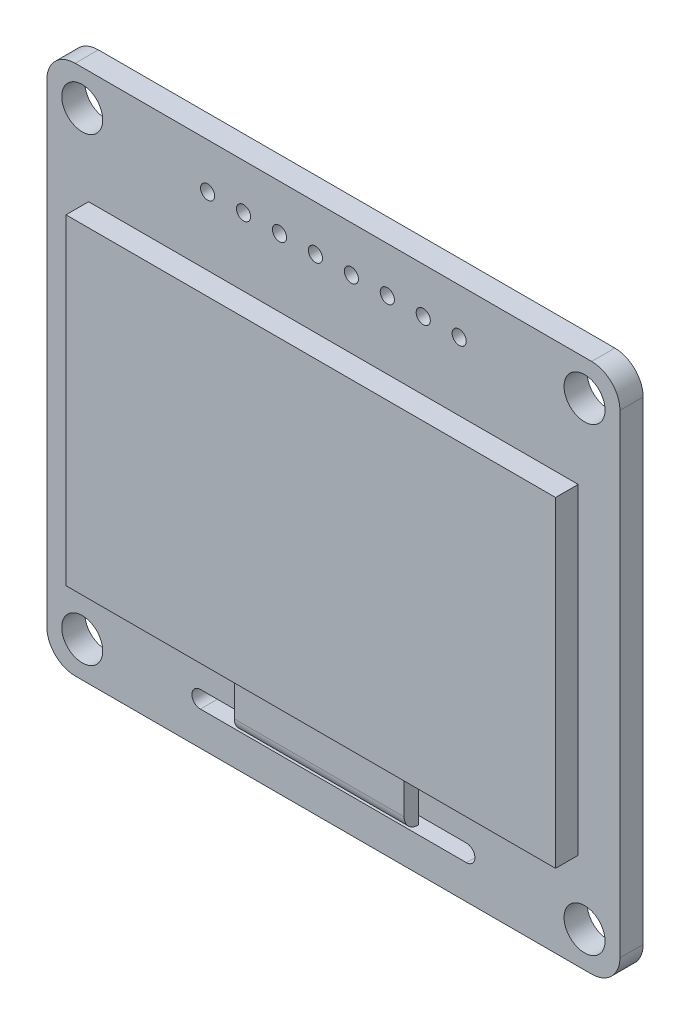
SolidWorks part; units mm, degrees
ref_plane "Front Plane" through (0, 0, 0) normal (0, 0, 1) x (1, 0, 0)
ref_plane "Top Plane" through (0, 0, 0) normal (0, 1, 0) x (1, 0, 0)
ref_plane "Right Plane" through (0, 0, 0) normal (1, 0, 0) x (0, 0, -1)
sketch "Sketch1" plane through (0, 0, 0) normal (0, 0, 1) x (1, 0, 0)
  line L0 (0, 18.75) -> (0, -18.75) construction
  line L1 (-20.25, 18.75) -> (20.25, 18.75)
  line L2 (-20.25, 18.75) -> (-20.25, -18.75)
  line L3 (-20.25, -18.75) -> (20.25, -18.75)
  line L4 (20.25, 18.75) -> (20.25, -18.75)
  point P6 (0, 0)
  dimension "D1" = 40.5
  dimension "D2" = 37.5
extrude "PCB" add sketch "Sketch1" along normal blind 1.64
fillet "Fillet1" radius 2 4 edges at (-20.25, -18.75, 0.82) (20.25, -18.75, 0.82) (20.25, 18.75, 0.82) (-20.25, 18.75, 0.82)
sketch "Sketch2" plane through (0, 0, 1.64) normal (0, 0, 1) x (1, 0, 0)
  line L0 (18.25, 18.75) -> (-18.25, 18.75) construction
  line L1 (-20.25, 16.75) -> (-20.25, -16.75) construction
  line L2 (20.25, -16.75) -> (20.25, 16.75) construction
  line L3 (-18.25, -18.75) -> (18.25, -18.75) construction
  circle A0 centre (-17.75, 16.25) radius 1.45
  circle A1 centre (17.75, 16.25) radius 1.45
  circle A2 centre (17.75, -16.25) radius 1.45
  circle A3 centre (-17.75, -16.25) radius 1.45
  dimension "D1" = 2.5
  dimension "D2" = 2.5
  dimension "D3" = 2.9
  dimension "D6" = 2.5
  dimension "D7" = 2.5
  dimension "D4" = 2
  dimension "D5" = 2
extrude "mount hole" cut sketch "Sketch2" against normal up to next
sketch "Sketch3" plane through (0, 0, 1.64) normal (0, 0, 1) x (1, 0, 0)
  line L0 (-9.4, -15.75) -> (9.4, -15.75) construction
  line L1 (-9.4, -15.15) -> (9.4, -15.15)
  line L2 (-9.4, -16.35) -> (9.4, -16.35)
  line L3 (0, 0) -> (0, -15.75) construction
  line L4 (-18.25, -18.75) -> (18.25, -18.75) construction
  arc A0 (-9.4, -15.15) -> (-9.4, -16.35) centre (-9.4, -15.75) ccw
  arc A1 (9.4, -16.35) -> (9.4, -15.15) centre (9.4, -15.75) ccw
  point P2 (0, -15.75)
  point P10 (10, -15.75)
  point P12 (-10, -15.75)
  dimension "D1" = 20
  dimension "D2" = 1.2
  dimension "D3" = 3
extrude "slot" cut sketch "Sketch3" against normal up to next
sketch "Sketch4" plane through (0, 0, 1.64) normal (0, 0, 1) x (1, 0, 0)
  line L0 (0, 0) -> (0, 18.75) construction
  line L1 (18.25, 18.75) -> (-18.25, 18.75) construction
  line L2 (-8.89, 15.55) -> (-6.35, 15.55) construction
  circle A0 centre (-8.89, 15.55) radius 0.5
  circle A1 centre (-6.35, 15.55) radius 0.5
  circle A2 centre (-3.81, 15.55) radius 0.5
  circle A3 centre (-1.27, 15.55) radius 0.5
  circle A4 centre (1.27, 15.55) radius 0.5
  circle A5 centre (3.81, 15.55) radius 0.5
  circle A6 centre (6.35, 15.55) radius 0.5
  circle A7 centre (8.89, 15.55) radius 0.5
  dimension "D2" = 1
  dimension "D5" = 1.27
  dimension "D1" = 3.2
  dimension "D4" = 2.54
  dimension "D3" = 8
extrude "Cut-Extrude3" cut sketch "Sketch4" against normal up to next
sketch "Sketch5" plane through (0, 0, 1.64) normal (0, 0, 1) x (1, 0, 0)
  line L0 (0, 10.75) -> (0, 18.75) construction
  line L1 (-17.3, 10.75) -> (17.3, 10.75)
  line L2 (-17.3, 10.75) -> (-17.3, -11.95)
  line L3 (-17.3, -11.95) -> (17.3, -11.95)
  line L4 (17.3, 10.75) -> (17.3, -11.95)
  line L5 (18.25, 18.75) -> (-18.25, 18.75) construction
  dimension "D1" = 34.6
  dimension "D2" = 22.7
  dimension "D3" = 8
extrude "OLED glass" add sketch "Sketch5" along normal blind 1.6
sketch "Sketch6" plane through (0, 0, 1.64) normal (0, 0, 1) x (1, 0, 0)
  line L0 (-17.3, -11.95) -> (17.3, -11.95) construction
  line L1 (-6, -11.95) -> (6, -11.95)
  line L2 (-6, -11.95) -> (-6, -15.75)
  line L3 (-6, -15.75) -> (6, -15.75)
  line L4 (6, -11.95) -> (6, -15.75)
  line L5 (9.4, -15.15) -> (-9.4, -15.15) construction
  line L6 (0, -15.15) -> (0, -15.75) construction
  point P8 (0, -15.15)
  dimension "D1" = 12
  dimension "D2" = 0.6
extrude "Boss-Extrude3" add sketch "Sketch6" along normal blind 1
fillet "Fillet2" radius 1 1 edges at (0, -15.75, 2.64)
sketch "Sketch7" plane through (0, 0, 3.24) normal (0, 0, 1) x (1, 0, 0)
  line L0 (60.8603, 140.4528) -> (115.3305, 140.4528) construction
